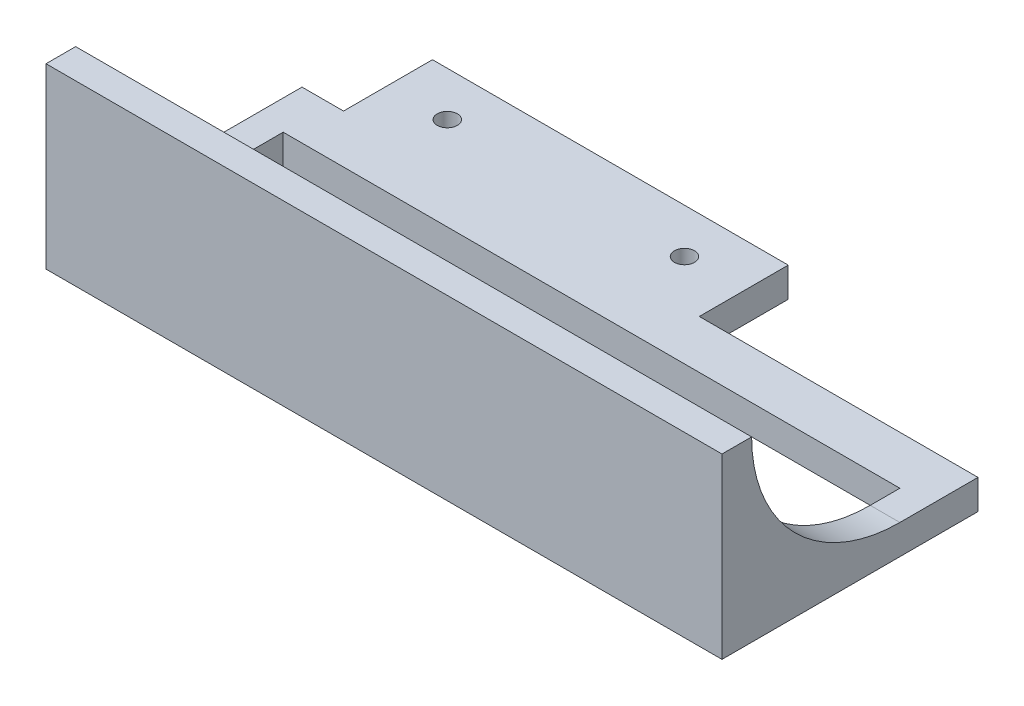
SolidWorks part; units mm, degrees
ref_plane "Front" through (0, 0, 0) normal (0, 0, 1) x (1, 0, 0)
ref_plane "Top" through (0, 0, 0) normal (0, 1, 0) x (1, 0, 0)
ref_plane "Right" through (0, 0, 0) normal (1, 0, 0) x (0, 0, -1)
sketch "Sketch1" plane through (0, 0, 0) normal (0, 1, 0) x (1, 0, 0)
  line L0 (0, 0) -> (0, -8.528)
  line L1 (0, -8.528) -> (67, -8.528)
  line L2 (67, -8.528) -> (67, -23.528)
  line L3 (67, -23.528) -> (114, -23.528)
  line L4 (114, -23.528) -> (114, -66.703)
  line L5 (114, -66.703) -> (0, -66.703)
  line L6 (0, -66.703) -> (0, 0)
  line L7 (5, -61.703) -> (109, -61.703)
  line L8 (109, -61.703) -> (109, -31.703)
  line L9 (109, -31.703) -> (5, -31.703)
  line L10 (5, -31.703) -> (5, -61.703)
  line L11 (7, -8.528) -> (7, -23.528)
  line L12 (7, -23.528) -> (0, -23.528)
  circle A0 centre (17, -16.028) radius 1.7
  circle A1 centre (57, -16.028) radius 1.7
  point P17 (30, -16.028)
  dimension "D10" = 15
  dimension "D2" = 104
  dimension "D3" = 60
  dimension "D4" = 5
  dimension "D5" = 10
  dimension "D6" = 5
  dimension "D7" = 30
  dimension "D8" = 7
  dimension "D9" = 40
extrude "Boss-Extrude1" add sketch "Sketch1" along normal blind 5 contours L11 L12 L6 L5 L4 L3 L2 L1 A1 A0 L10 L9 L8 L7 region at (37, 0, 9.8079)
sketch "Sketch2" plane through (0, 5, 0) normal (0, 1, 0) x (1, 0, 0)
  line L0 (5, -61.703) -> (0, -61.703)
  line L1 (0, -66.703) -> (0, -23.528) construction
  line L2 (0, -61.703) -> (0, -66.703)
  line L3 (0, -66.703) -> (114, -66.703)
  line L4 (114, -66.703) -> (114, -61.703)
  line L5 (114, -23.528) -> (114, -66.703) construction
  line L6 (114, -61.703) -> (5, -61.703)
extrude "Boss-Extrude2" add sketch "Sketch2" along normal blind 25
fillet "Fillet1" radius 25 2 edges at (2.5, 5, 61.703) (111.5, 5, 61.703)
